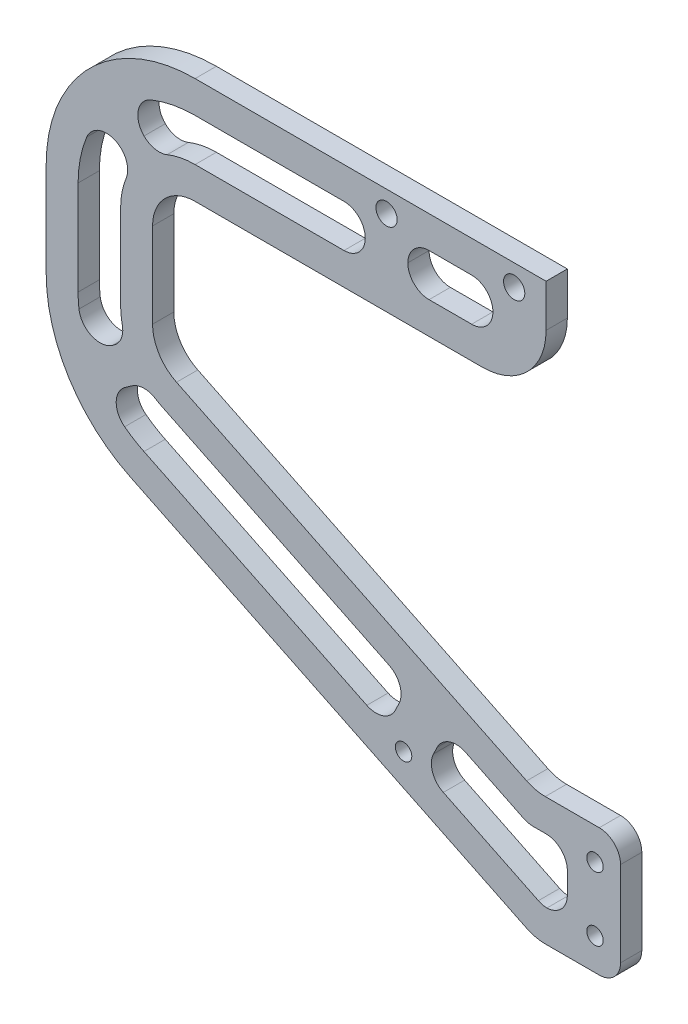
SolidWorks part; units mm, degrees
material "6061 Alloy"
ref_plane "Front Plane" through (0, 0, 0) normal (0, 0, 1) x (1, 0, 0)
ref_plane "Top Plane" through (0, 0, 0) normal (0, 1, 0) x (1, 0, 0)
ref_plane "Right Plane" through (0, 0, 0) normal (1, 0, 0) x (0, 0, -1)
sketch "Sketch1" plane through (0, 0, 0) normal (0, 0, 1) x (1, 0, 0)
  line L0 (0, 0) -> (0, 38.1)
  line L1 (0, 38.1) -> (-25.4, 38.1)
  line L2 (-139.7, 101.6) -> (-139.7, 127)
  line L3 (-127, 139.7) -> (-22.225, 139.7)
  line L4 (-22.225, 139.7) -> (-22.225, 171.45)
  line L5 (-22.225, 171.45) -> (-127, 171.45)
  line L6 (-171.45, 127) -> (-171.45, 98.8013)
  line L7 (0, 0) -> (-25.4, 0)
  line L8 (-146.4302, 58.8229) -> (-25.4, 0)
  line L9 (0, 19.05) -> (25.4, 19.05) construction
  line L10 (25.4, 19.05) -> (25.4, 120.65) construction
  line L11 (25.4, 120.65) -> (-127, 120.65) construction
  line L12 (-25.4, 38.1) -> (-132.5515, 90.1776)
  line L13 (0, 19.05) -> (-7.62, 19.05) construction
  line L14 (-7.62, 28.575) -> (-7.62, 9.525) construction
  line L15 (-7.62, 28.575) -> (-64.77, 28.575) construction
  line L16 (-69.85, 166.6875) -> (-31.75, 166.6875) construction
  line L17 (-50.8, 166.6875) -> (-50.8, 120.65) construction
  line L18 (-127, 120.65) -> (-127, 101.6) construction
  arc A0 (-171.45, 98.8013) -> (-146.4302, 58.8229) centre (-127, 98.8013) ccw
  arc A1 (-127, 171.45) -> (-171.45, 127) centre (-127, 127) ccw
  arc A2 (-139.7, 127) -> (-127, 139.7) centre (-127, 127) cw
  arc A3 (-132.5515, 90.1776) -> (-139.7, 101.6) centre (-127, 101.6) cw
  circle A7 centre (-31.75, 166.6875) radius 3.175 construction
  circle A8 centre (-69.85, 166.6875) radius 3.175 construction
  point P26 (-50.8, 166.6875)
  point P28 (-50.8, 120.65)
  dimension "D9" = 44.45
  dimension "D10" = 12.7
  dimension "D22" = 6.35
  dimension "D8" = 44.45
  dimension "D1" = 38.1
  dimension "D3" = 31.75
  dimension "D4" = 31.75
  dimension "D5" = 19.05
  dimension "D6" = 19.05
  dimension "D7" = 57.15
  dimension "D11" = 25.4
  dimension "D12" = 101.6
  dimension "D13" = 152.4
  dimension "D14" = 25.4
  dimension "D15" = 19.05
  dimension "D17" = 7.62
  dimension "D19" = 4.7625
  dimension "D20" = 38.1
  dimension "D21" = 9.525
extrude "Boss-Extrude1" add sketch "Sketch1" along normal blind 6.35
hole_wizard "1/4 (0.25) Diameter Hole1" positions "Sketch3" profile "Sketch2" hole size "1/4" standard "ANSI Inch"
sketch "Sketch3" plane through (0, 0, 6.35) normal (0, 0, 1) x (1, 0, 0)
  line L0 (-69.85, 165.1) -> (-22.225, 165.1) construction
  line L1 (-22.225, 139.7) -> (-22.225, 171.45) construction
  line L3 (-22.225, 171.45) -> (-127, 171.45) construction
  point P4 (-69.85, 165.1)
  point P6 (-31.75, 165.1)
  dimension "D1" = 9.525
  dimension "D2" = 38.1
  dimension "D3" = 6.35
sketch "Sketch2" plane through (-69.85, 165.1, 6.35) normal (1, 0, 0) x (0, -1, 0)
  line L0 (0, 0) -> (0, 11.5597)
  line L1 (0, 11.5597) -> (3.175, 9.652)
  line L2 (3.175, 9.652) -> (3.175, 0)
  line L5 (3.175, 0) -> (0, 0)
  line L10 (0, 11.5597) -> (-3.175, 9.652) construction
  line L11 (0, -6.35) -> (0, 107.95) construction
  dimension "Hole Dia." = 6.35
  dimension "Hole Depth" = 9.652
  dimension "Drill Angle" = 118
hole_wizard "#10 (0.1935) Diameter Hole1" positions "Sketch5" profile "Sketch4" hole size "#10" standard "ANSI Inch"
sketch "Sketch5" plane through (0, 0, 6.35) normal (0, 0, 1) x (1, 0, 0)
  line L0 (-7.62, 28.575) -> (-7.62, 9.525) construction
  line L2 (0, 19.05) -> (-7.62, 19.05) construction
  line L3 (0, 0) -> (0, 38.1) construction
  line L6 (-64.77, 28.575) -> (-7.62, 28.575) construction
  point P0 (-7.62, 28.575)
  point P2 (-7.62, 9.525)
  point P18 (-64.77, 28.575)
  dimension "D1" = 19.05
  dimension "D2" = 7.62
  dimension "D3" = 57.15
sketch "Sketch4" plane through (-7.62, 28.575, 6.35) normal (1, 0, 0) x (0, -1, 0)
  line L0 (0, 0) -> (0, 11.1286)
  line L1 (0, 11.1286) -> (2.4574, 9.652)
  line L2 (2.4574, 9.652) -> (2.4574, 0)
  line L5 (2.4574, 0) -> (0, 0)
  line L10 (0, 11.1286) -> (-2.4575, 9.652) construction
  line L11 (0, -6.35) -> (0, 107.95) construction
  dimension "Hole Dia." = 4.9149
  dimension "Hole Depth" = 9.652
  dimension "Drill Angle" = 118
fillet "Fillet1" radius 12.7 2 edges at (-25.4, 0, 3.175) (-25.4, 38.1, 3.175)
fillet "Fillet2" radius 6.35 2 edges at (0, 0, 3.175) (0, 38.1, 3.175)
sketch "Sketch7" plane through (0, 0, 6.35) normal (0, 0, 1) x (1, 0, 0)
  line L0 (-12.7, 28.575) -> (-22.4772, 28.575)
  line L1 (-32.1924, 30.8108) -> (-51.9549, 40.4158)
  line L2 (-58.6067, 26.7295) -> (-23.8651, 9.8444)
  line L3 (-22.4772, 9.525) -> (-12.7, 9.525)
  line L4 (-12.7, 28.575) -> (-12.7, 9.525)
  line L5 (-58.6067, 26.7295) -> (-51.9549, 40.4158)
  line L6 (-32.1924, 30.8108) -> (-136.7151, 81.6108) construction
  line L7 (-142.2666, 67.3897) -> (-23.8651, 9.8444) construction
  line L8 (-22.4772, 9.525) -> (-6.35, 9.525) construction
  line L9 (-6.35, 28.575) -> (-22.4772, 28.575) construction
  line L10 (-22.4772, 0) -> (-6.35, 0)
  line L11 (0, 6.35) -> (0, 31.75)
  line L12 (-6.35, 38.1) -> (-22.4772, 38.1)
  line L13 (-28.0287, 39.3776) -> (-132.5515, 90.1776)
  line L14 (-139.7, 101.6) -> (-139.7, 127)
  line L15 (-127, 139.7) -> (-22.225, 139.7)
  line L16 (-22.225, 139.7) -> (-22.225, 171.45)
  line L17 (-22.225, 171.45) -> (-127, 171.45)
  line L18 (-171.45, 127) -> (-171.45, 98.8013)
  line L19 (-146.4302, 58.8229) -> (-28.0287, 1.2776)
  line L20 (-161.925, 133.35) -> (-161.925, 95.25)
  line L21 (0, 6.35) -> (0, 31.75) construction
  line L22 (-161.925, 95.25) -> (-149.225, 95.25)
  line L23 (-149.225, 133.35) -> (-149.225, 95.25)
  line L24 (-139.7, 101.6) -> (-139.7, 127) construction
  line L25 (-127, 139.7) -> (-22.225, 139.7) construction
  line L26 (-22.225, 139.7) -> (-22.225, 171.45) construction
  line L27 (-22.225, 171.45) -> (-127, 171.45) construction
  line L28 (-171.45, 127) -> (-171.45, 98.8013) construction
  line L29 (-149.225, 133.35) -> (-161.925, 133.35)
  line L30 (-133.35, 158.75) -> (-133.35, 146.05)
  line L31 (-133.35, 146.05) -> (-79.375, 146.05)
  line L32 (-79.375, 146.05) -> (-79.375, 158.75)
  line L33 (-28.0287, 39.3776) -> (-132.5515, 90.1776) construction
  line L34 (-28.0287, 39.3776) -> (-132.5515, 90.1776)
  line L35 (-79.375, 158.75) -> (-133.35, 158.75)
  line L36 (-28.0287, 39.3776) -> (-132.5515, 90.1776) construction
  line L37 (-146.4302, 58.8229) -> (-28.0287, 1.2776) construction
  line L38 (-22.4772, 0) -> (-6.35, 0) construction
  line L39 (-6.35, 38.1) -> (-22.4772, 38.1) construction
  line L40 (-60.325, 158.75) -> (-60.325, 146.05)
  line L41 (-60.325, 146.05) -> (-41.275, 146.05)
  line L42 (-41.275, 146.05) -> (-41.275, 158.75)
  line L43 (-41.275, 158.75) -> (-60.325, 158.75)
  line L49 (-131.9116, 79.2762) -> (-63.3773, 45.9673)
  line L50 (-63.3773, 45.9673) -> (-70.0291, 32.281)
  line L51 (-70.0291, 32.281) -> (-138.5634, 65.5899)
  line L52 (-138.5634, 65.5899) -> (-131.9116, 79.2762)
  line L53 (-146.4302, 58.8229) -> (-28.0287, 1.2776) construction
  line L54 (-58.6067, 26.7295) -> (-70.0291, 32.281) construction
  line L55 (-64.77, 28.575) -> (-53.5025, 51.7583) construction
  arc A0 (-32.1924, 30.8108) -> (-22.4772, 28.575) centre (-22.4772, 50.8) ccw
  arc A1 (-23.8651, 9.8444) -> (-22.4772, 9.525) centre (-22.4772, 12.7) ccw
  circle A2 centre (-69.85, 165.1) radius 3.175 construction
  circle A3 centre (-31.75, 165.1) radius 3.175 construction
  arc A8 (-6.35, 0) -> (0, 6.35) centre (-6.35, 6.35) ccw
  arc A9 (0, 31.75) -> (-6.35, 38.1) centre (-6.35, 31.75) ccw
  arc A10 (-28.0287, 39.3776) -> (-22.4772, 38.1) centre (-22.4772, 50.8) ccw
  arc A11 (-139.7, 101.6) -> (-132.5515, 90.1776) centre (-127, 101.6) ccw
  arc A12 (-127, 139.7) -> (-139.7, 127) centre (-127, 127) ccw
  arc A13 (-127, 171.45) -> (-171.45, 127) centre (-127, 127) ccw
  arc A14 (-171.45, 98.8013) -> (-146.4302, 58.8229) centre (-127, 98.8013) ccw
  arc A15 (-28.0287, 1.2776) -> (-22.4772, 0) centre (-22.4772, 12.7) ccw
  arc A16 (-6.35, 0) -> (0, 6.35) centre (-6.35, 6.35) ccw construction
  arc A17 (0, 31.75) -> (-6.35, 38.1) centre (-6.35, 31.75) ccw construction
  arc A18 (-28.0287, 39.3776) -> (-22.4772, 38.1) centre (-22.4772, 50.8) ccw construction
  arc A19 (-139.7, 101.6) -> (-132.5515, 90.1776) centre (-127, 101.6) ccw construction
  arc A20 (-127, 139.7) -> (-139.7, 127) centre (-127, 127) ccw construction
  arc A21 (-127, 171.45) -> (-171.45, 127) centre (-127, 127) ccw construction
  arc A22 (-171.45, 98.8013) -> (-146.4302, 58.8229) centre (-127, 98.8013) ccw construction
  arc A23 (-28.0287, 1.2776) -> (-22.4772, 0) centre (-22.4772, 12.7) ccw construction
  point P46 (-64.3179, 29.5052)
  point P63 (-149.225, 114.3)
  point P64 (-139.7, 114.3)
  dimension "D11" = 9.525
  dimension "D3" = 9.525
  dimension "D4" = 9.525
  dimension "D5" = 12.7
  dimension "D6" = 12.7
  dimension "D7" = 76.2
  dimension "D8" = 38.1
  dimension "D9" = 9.525
  dimension "D10" = 9.525
  dimension "D12" = 9.525
  dimension "D13" = 6.35
  dimension "D14" = 12.7
  dimension "D15" = 9.525
  dimension "D16" = 53.975
  dimension "D1" = 0
  dimension "D2" = 9.525
extrude "Cut-Extrude2" [suppressed] cut sketch "Sketch7" against normal up to next contours L52 L51 L50 L49 | L23 L29 L20 L22 | L32 L35 L30 L31 | L42 L43 L40 L41 | L5 L1 A0 L0 L4 L3 A1 L2
fillet "Fillet3" [suppressed] radius 6.35
sketch "Sketch8" plane through (0, 0, 6.35) normal (0, 0, 1) x (1, 0, 0)
  line L0 (-158.4309, 158.4309) -> (-135.9803, 135.9803) construction
  line L1 (-164.6794, 75.2203) -> (-137.4037, 94.3163) construction
  line L2 (-53.5025, 51.7583) -> (-68.4815, 20.9384) construction
  line L3 (-28.0287, 39.3776) -> (-132.5515, 90.1776) construction
  line L4 (-146.4302, 58.8229) -> (-28.0287, 1.2776) construction
  line L5 (-123.6324, 130.3676) -> (-130.3676, 123.6324) construction
  line L6 (-101.6, 171.45) -> (-101.6, 161.925) construction
  line L7 (-22.225, 171.45) -> (-127, 171.45) construction
  line L8 (-101.6, 139.7) -> (-101.6, 149.225) construction
  line L9 (-127, 139.7) -> (-22.225, 139.7) construction
  line L10 (-76.2, 161.925) -> (-127, 161.925)
  line L11 (-127, 149.225) -> (-76.2, 149.225)
  line L12 (-76.2, 149.225) -> (-76.2, 161.925)
  line L13 (-148.0974, 154.8326) -> (-138.9828, 145.718)
  line L14 (-69.85, 171.45) -> (-69.85, 139.7) construction
  line L15 (-31.75, 171.45) -> (-31.75, 139.7) construction
  line L16 (-161.925, 127) -> (-161.925, 98.8013)
  line L17 (-149.225, 127) -> (-149.225, 101.6)
  line L18 (-154.8326, 148.0974) -> (-145.718, 138.9828)
  line L19 (-153.5499, 88.8258) -> (-148.0871, 81.023) construction
  line L20 (-159.0667, 84.9635) -> (-147.515, 93.0509)
  line L21 (-142.0522, 85.2482) -> (-154.1221, 76.7979)
  line L22 (-136.7151, 81.6108) -> (-63.3773, 45.9673)
  line L23 (-142.2666, 67.3897) -> (-70.0291, 32.281)
  line L24 (-70.4812, 31.3507) -> (-59.0588, 25.7993) construction
  line L25 (-70.0291, 32.281) -> (-63.3773, 45.9673)
  line L26 (-76.2, 155.575) -> (-63.5, 155.575) construction
  line L27 (-51.9549, 40.4158) -> (-27.5921, 28.575)
  line L28 (-27.5921, 28.575) -> (-15.875, 28.575)
  line L29 (-15.875, 28.575) -> (-15.875, 9.525)
  line L30 (-15.875, 9.525) -> (-23.2079, 9.525)
  line L31 (-23.2079, 9.525) -> (-58.6067, 26.7295)
  line L32 (-58.6067, 26.7295) -> (-51.9549, 40.4158)
  line L34 (0, 6.35) -> (0, 31.75) construction
  line L35 (-15.875, 9.525) -> (-15.875, 0) construction
  line L36 (-22.4772, 0) -> (-6.35, 0) construction
  line L37 (-15.875, 28.575) -> (-15.875, 38.1) construction
  line L38 (-6.35, 38.1) -> (-22.4772, 38.1) construction
  line L39 (-38.1, 155.575) -> (-25.4, 155.575) construction
  line L41 (-63.5, 161.925) -> (-38.1, 161.925)
  line L42 (-63.5, 161.925) -> (-63.5, 149.225)
  line L43 (-63.5, 149.225) -> (-38.1, 149.225)
  line L44 (-38.1, 161.925) -> (-38.1, 149.225)
  arc A0 (-127, 171.45) -> (-171.45, 127) centre (-127, 127) ccw construction
  arc A1 (-127, 139.7) -> (-139.7, 127) centre (-127, 127) ccw construction
  arc A2 (-171.45, 98.8013) -> (-146.4302, 58.8229) centre (-127, 98.8013) ccw construction
  arc A3 (-139.7, 101.6) -> (-132.5515, 90.1776) centre (-127, 101.6) ccw construction
  arc A4 (-127, 149.225) -> (-138.9828, 145.718) centre (-127, 127) ccw
  arc A5 (-127, 161.925) -> (-148.0974, 154.8326) centre (-127, 127) ccw
  arc A6 (-145.718, 138.9828) -> (-149.225, 127) centre (-127, 127) ccw
  arc A7 (-154.8326, 148.0974) -> (-161.925, 127) centre (-127, 127) ccw
  arc A8 (-149.225, 101.6) -> (-147.515, 93.0509) centre (-127, 101.6) ccw
  arc A9 (-161.925, 98.8013) -> (-159.0667, 84.9635) centre (-127, 98.8013) ccw
  arc A10 (-142.0522, 85.2482) -> (-136.7151, 81.6108) centre (-127, 101.6) ccw
  arc A11 (-154.1221, 76.7979) -> (-142.2666, 67.3897) centre (-127, 98.8013) ccw
  point P8 (-127, 127)
  point P9 (-127, 127)
  point P18 (-127, 101.6)
  point P19 (-150.8185, 84.9244)
  point P26 (-64.77, 28.575)
  point P47 (-69.85, 165.1)
  point P48 (-31.75, 165.1)
  point P77 (-69.85, 155.575)
  point P94 (-31.75, 155.575)
  dimension "D1" = 9.525
  dimension "D2" = 9.525
  dimension "D3" = 12.7
  dimension "D4" = 12.7
  dimension "D5" = 15.875
extrude "Cut-Extrude3" cut sketch "Sketch8" against normal through all
fillet "Fillet4" radius 6.35 22 edges at (-27.5921, 28.575, 3.175) (-23.2079, 9.525, 3.175) (-15.875, 9.525, 3.175) (-15.875, 28.575, 3.175) (-58.6067, 26.7295, 3.175) (-51.9549, 40.4158, 3.175) (-63.3773, 45.9673, 3.175) (-70.0291, 32.281, 3.175) (-154.1221, 76.7979, 3.175) (-142.0522, 85.2482, 3.175) (-147.515, 93.0509, 3.175) (-159.0667, 84.9635, 3.175) (-154.8326, 148.0974, 3.175) (-145.718, 138.9828, 3.175) (-138.9828, 145.718, 3.175) (-148.0974, 154.8326, 3.175) (-76.2, 149.225, 3.175) (-76.2, 161.925, 3.175) (-38.1, 149.225, 3.175) (-38.1, 161.925, 3.175) (-63.5, 149.225, 3.175) (-63.5, 161.925, 3.175)
fillet "Fillet5" radius 19.05 1 edges at (-22.225, 139.7, 3.175)
